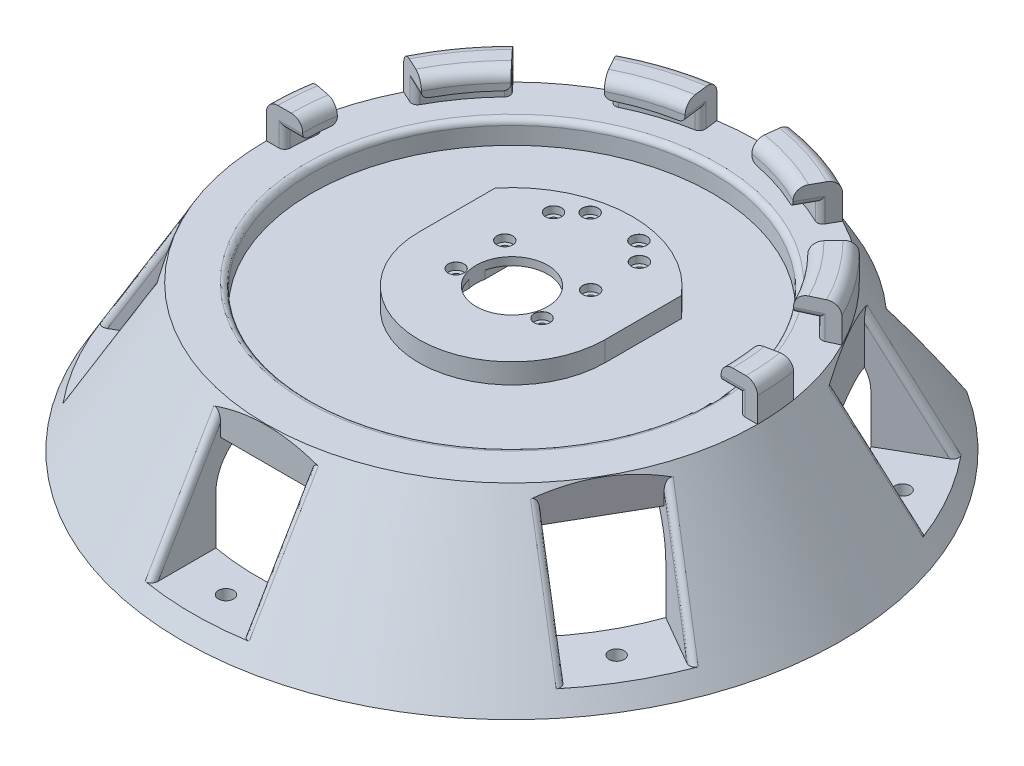
SolidWorks part; units mm, degrees
note: The reader was unsure of these and kept them because the rebuilt part matched: shared geometry of "Sketch3<3>".
material "PLA"
ref_plane "Front Plane" through (0, 0, 0) normal (0, 0, 1) x (1, 0, 0)
ref_plane "Top Plane" through (0, 0, 0) normal (0, 1, 0) x (1, 0, 0)
ref_plane "Right Plane" through (0, 0, 0) normal (1, 0, 0) x (0, 0, -1)
sketch "Sketch1" plane through (0, 0, 0) normal (0, 0, 1) x (1, 0, 0)
  line L0 (0, 0) -> (-85.725, 0)
  line L1 (-85.725, 0) -> (-115.0544, -50.8)
  line L2 (-115.0544, -50.8) -> (0, -50.8)
  line L6 (0, 0) -> (0, -50.8) construction
  line L7 (0, 0) -> (0, -50.8)
  dimension "D1" = 85.725
  dimension "D3" = 50.8
  dimension "D4" = 60
revolve "Revolve1" add sketch "Sketch1" angle 360 about L6
sketch "Sketch2" plane through (0, 0, 0) normal (0, 1, 0) x (1, 0, 0)
  circle A0 centre (0, 0) radius 12.5
  dimension "D1" = 25
extrude "Cut-Extrude1" cut sketch "Sketch2" against normal through all
sketch "Sketch3" plane through (0, 0, 0) normal (0, 1, 0) x (1, 0, 0)
  line L0 (-32.5, 0) -> (-32.5, 26.6036)
  line L1 (-32.5, 26.6036) -> (32.5, 26.6036)
  line L2 (32.5, 26.6036) -> (32.5, 0)
  circle A0 centre (0, 0) radius 32.5
  circle A1 centre (0, 0) radius 70
  circle A2 centre (0, 0) radius 42
  circle M1 centre (0, 0) radius 12.5
  dimension "D1" = 65
  dimension "D2" = 140
  dimension "D3" = 84
extrude "Cut-Extrude2" cut sketch "Sketch3" against normal blind 8 contours A1 A0 L0 L1 L2 | A1 A2
sketch "Sketch7" plane through (0, -50.8, 0) normal (0, -1, 0) x (1, 0, 0)
  line L0 (0, 88.9) -> (0, -161.1) construction
  line L1 (-85.4, 0) -> (85.4, 0) construction
  line L2 (-60, -65.5989) -> (-60, -161.1)
  line L3 (-60, -161.1) -> (60, -161.1)
  line L4 (60, -161.1) -> (60, -65.5989)
  line L5 (-60, -65.5989) -> (60, -65.5989) construction
  arc A2 (60, -65.5989) -> (-60, -65.5989) centre (0, 0) ccw
  dimension "D1" = 177.8
  dimension "D2" = 25.4
  dimension "D3" = 25.4
  dimension "D4" = 120
  dimension "D5" = 250
extrude "Cut-Extrude5" cut sketch "Sketch7" against normal blind 39 contours L3 L4 A2 L2
sketch "Sketch8" plane through (0, 0, 0) normal (0, 1, 0) x (1, 0, 0)
  line L0 (0, 0) -> (0, -115.0544) construction
  line L2 (-15.875, -123.925) -> (15.875, -123.925)
  line L3 (-15.875, -123.925) -> (-15.875, -85.825)
  line L4 (-15.875, -85.825) -> (15.875, -85.825)
  line L5 (15.875, -123.925) -> (15.875, -85.825)
  line L6 (-15.875, -123.925) -> (15.875, -85.825) construction
  line L7 (-15.875, -85.825) -> (15.875, -123.925) construction
  arc A0 (-60, 98.1708) -> (60, 98.1708) centre (0, 0) ccw construction
  point P6 (0, -104.875)
  dimension "D1" = 85.825
  dimension "D2" = 38.1
  dimension "D3" = 31.75
extrude "Cut-Extrude6" cut sketch "Sketch8" against normal blind 44.45
pattern_circular "CirPattern2" count 6 over 360 about axis through (0, 0, 0) along (0, 1, 0) of "Cut-Extrude6"
sketch "Sketch9" plane through (0, 0, 0) normal (0, 1, 0) x (1, 0, 0)
  line L0 (0, 0) -> (0, -115.0544) construction
  arc A0 (-60, 98.1708) -> (60, 98.1708) centre (0, 0) ccw construction
  circle A1 centre (0, -99.8144) radius 2.65
  dimension "D1" = 5.3
  dimension "D2" = 15.24
extrude "Cut-Extrude7" cut sketch "Sketch9" against normal through all
pattern_circular "CirPattern3" count 6 over 360 about axis through (0, 0, 0) along (0, 1, 0) of "Cut-Extrude7"
sketch "Sketch12" plane through (0, 0, 0) normal (0, 0, 1) x (1, 0, 0)
  line L0 (85.725, 0) -> (85.725, 12.7)
  line L1 (85.725, 12.7) -> (73.025, 12.7)
  line L2 (73.025, 12.7) -> (73.025, 6.35)
  line L3 (73.025, 6.35) -> (79.375, 6.35)
  line L4 (79.375, 6.35) -> (79.375, 0)
  line L5 (85.725, 0) -> (-85.725, 0) construction
  line L6 (0, 0) -> (0, 12.7) construction
  line L7 (12.5, 0) -> (-12.5, 0) construction
  line L8 (79.375, 0) -> (85.725, 0)
  point P13 (0, 6.35)
  dimension "D1" = 6.35
  dimension "D2" = 73.025
  dimension "D3" = 79.375
  dimension "D4" = 12.7
  dimension "D5" = 12.7
revolve "Revolve2" add sketch "Sketch12" angle 180 about L6
sketch "Sketch15" plane through (0, -11.8, 0) normal (0, -1, 0) x (1, 0, 0)
  line L0 (0, -1000) -> (0, 49000) construction
  point P1 (-15, 4.5)
  point P4 (-15, -12.5)
  point P5 (-15, -29.5)
  point P6 (-8.5, -35.8)
  point P7 (8.5, -35.8)
  point P8 (15, -29.5)
  point P9 (15, -12.5)
  point P10 (15, 4.5)
  dimension "D1" = 17
  dimension "D2" = 17
  dimension "D3" = 4.5
  dimension "D4" = 15
  dimension "D5" = 8.5
  dimension "D6" = 35.8
sketch "Sketch18" plane through (0, 12.7, 0) normal (0, 1, 0) x (1, 0, 0)
  line L0 (46.6433, 89.7185) -> (70.9138, 72.0849)
  line L1 (0, 201000) -> (0, -249000) construction
  line L2 (-15, 100) -> (-9, 50)
  line L3 (-9, 50) -> (9, 50)
  line L4 (9, 50) -> (15, 100)
  line L5 (-15, 100) -> (15, 100)
  line L6 (36.6704, 35.1608) -> (70.9138, 72.0849)
  line L7 (22.1081, 45.7409) -> (36.6704, 35.1608)
  line L8 (46.6433, 89.7185) -> (22.1081, 45.7409)
  line L9 (90.4704, 45.1675) -> (99.7409, 16.6359)
  line L10 (50.334, 6.8913) -> (99.7409, 16.6359)
  line L11 (44.7717, 24.0104) -> (50.334, 6.8913)
  line L12 (90.4704, 45.1675) -> (44.7717, 24.0104)
  line L13 (99.7409, -16.6359) -> (90.4704, -45.1675)
  line L14 (44.7717, -24.0104) -> (90.4704, -45.1675)
  line L15 (50.334, -6.8913) -> (44.7717, -24.0104)
  line L16 (99.7409, -16.6359) -> (50.334, -6.8913)
  line L17 (70.9138, -72.0849) -> (46.6433, -89.7185)
  line L18 (22.1081, -45.7409) -> (46.6433, -89.7185)
  line L19 (36.6704, -35.1608) -> (22.1081, -45.7409)
  line L20 (70.9138, -72.0849) -> (36.6704, -35.1608)
  line L21 (15, -100) -> (-15, -100)
  line L22 (-9, -50) -> (-15, -100)
  line L23 (9, -50) -> (-9, -50)
  line L24 (15, -100) -> (9, -50)
  line L25 (-46.6433, -89.7185) -> (-70.9138, -72.0849)
  line L26 (-36.6704, -35.1608) -> (-70.9138, -72.0849)
  line L27 (-22.1081, -45.7409) -> (-36.6704, -35.1608)
  line L28 (-46.6433, -89.7185) -> (-22.1081, -45.7409)
  line L29 (-90.4704, -45.1675) -> (-99.7409, -16.6359)
  line L30 (-50.334, -6.8913) -> (-99.7409, -16.6359)
  line L31 (-44.7717, -24.0104) -> (-50.334, -6.8913)
  line L32 (-90.4704, -45.1675) -> (-44.7717, -24.0104)
  line L33 (-99.7409, 16.6359) -> (-90.4704, 45.1675)
  line L34 (-44.7717, 24.0104) -> (-90.4704, 45.1675)
  line L35 (-50.334, 6.8913) -> (-44.7717, 24.0104)
  line L36 (-99.7409, 16.6359) -> (-50.334, 6.8913)
  line L37 (-70.9138, 72.0849) -> (-46.6433, 89.7185)
  line L38 (-22.1081, 45.7409) -> (-46.6433, 89.7185)
  line L39 (-36.6704, 35.1608) -> (-22.1081, 45.7409)
  line L40 (-70.9138, 72.0849) -> (-36.6704, 35.1608)
  point P4 (0, 50)
  point P7 (0, 100)
  point P48 (0, 0)
  dimension "D1" = 18
  dimension "D2" = 50
  dimension "D3" = 30
  dimension "D4" = 50
  dimension "D5" = 10
extrude "Cut-Extrude9" cut sketch "Sketch18" against normal blind 12.7
sketch "Sketch20" plane through (0, -11.8, 0) normal (0, -1, 0) x (1, 0, 0)
  line L0 (-22.5, -33) -> (-12.5, -40)
  line L1 (22.5, 20) -> (-22.5, 20)
  line L2 (22.5, 20) -> (22.5, -40)
  line L3 (22.5, -40) -> (-22.5, -40)
  line L4 (-22.5, 20) -> (-22.5, -40)
  line L5 (22.5, 20) -> (-22.5, -40) construction
  line L6 (22.5, -40) -> (-22.5, 20) construction
  line L7 (-12.5, -40) -> (12.5, -40)
  line L8 (12.5, -40) -> (22.5, -33)
  point P0 (0, -10)
  dimension "D1" = 60
  dimension "D2" = 45
  dimension "D3" = 10
  dimension "D4" = 10
  dimension "D5" = 7
  dimension "D6" = 7
  dimension "D7" = 10
extrude "Cut-Extrude11" cut sketch "Sketch3<3>" against normal blind 1 contours A0 L1 M1 | A0 L1 L0 | L1 A0 | L1 A2 A0 | A0 L2 L1
sketch "Sketch3<3>" plane through (0, 0, 0) normal (0, 1, 0) x (1, 0, 0) same geometry as "Sketch3"
sketch "Sketch22" plane through (0, -1, 0) normal (0, 1, 0) x (1, 0, 0)
  circle A0 centre (-15, 12.5) radius 1.4
  circle A1 centre (-15, 29.5) radius 1.4
  circle A2 centre (-8.5, 35.8) radius 1.4
  circle A3 centre (8.5, 35.8) radius 1.4
  circle A4 centre (15, 29.5) radius 1.4
  circle A5 centre (15, 12.5) radius 1.4
  circle A6 centre (15, -4.5) radius 1.4
  circle A7 centre (-15, -4.5) radius 1.4
  dimension "D1" = 17
  dimension "D2" = 17
  dimension "D3" = 2.8
  dimension "D4" = 2.8
  dimension "D5" = 2.8
  dimension "D6" = 2.8
  dimension "D7" = 2.8
  dimension "D8" = 2.8
  dimension "D9" = 2.8
  dimension "D10" = 2.8
  dimension "D11" = 17
  dimension "D12" = 30
  dimension "D13" = 30
  dimension "D14" = 30
  dimension "D15" = 17
  dimension "D16" = 17
  dimension "D17" = 6.3
  dimension "D18" = 6.3
  dimension "D19" = 35.8
  dimension "D20" = 8.5
  dimension "D21" = 35.8
  dimension "D22" = 15
  dimension "D23" = 19.5256
  dimension "D24" = 15.6605
hole_wizard "CBORE for M2.5 SHCS1" positions "Sketch23" profile "Sketch24" counterbore size "M2.5" standard "ANSI Metric" end condition through all
sketch "Sketch23" plane through (0, -1, 0) normal (0, 1, 0) x (1, 0, 0)
  point P0 (-15, -4.5)
  point P3 (-15, 12.5)
  point P6 (-15, 29.5)
  point P9 (-8.5, 35.8)
  point P12 (8.5, 35.8)
  point P15 (15, 29.5)
  point P18 (15, 12.5)
  point P21 (15, -4.5)
sketch "Sketch24" plane through (-15, -1, 4.5) normal (1, 0, 0) x (0, 0, 1)
  line L0 (0, 0) -> (0, 49.8)
  line L1 (0, 49.8) -> (1.45, 49.8)
  line L3 (1.45, 49.8) -> (1.45, 2.5)
  line L4 (2.75, 2.5) -> (1.45, 2.5)
  line L5 (2.75, 2.5) -> (2.75, 0.025)
  line L6 (2.75, 0.025) -> (2.775, 0)
  line L7 (2.775, 0) -> (0, 0)
  line L8 (-2.75, 0.025) -> (-2.775, 0) construction
  line L11 (0, -6.35) -> (0, 107.95) construction
  dimension "Thru Hole Dia." = 2.9
  dimension "Thru Hole Depth" = 49.8
  dimension "C'Bore Dia." = 5.5
  dimension "C'Bore Depth" = 2.5
  dimension "Near C'Sink Dia." = 5.55
  dimension "Near C'Sink Angle" = 90
fillet "Fillet1" radius 4 12 edges at (85.4509, 12.7, -6.8497) (69.353, 12.7, -50.3879) (26.4905, 12.7, -81.5293) (-26.4905, 12.7, -81.5293) (-69.353, 12.7, -50.3879) (-85.4509, 12.7, -6.8497) (-72.8088, 12.7, -5.6148) (-59.0785, 12.7, -42.923) (-22.566, 12.7, -69.4509) (22.566, 12.7, -69.4509) (59.0785, 12.7, -42.923) (72.8088, 12.7, -5.6148)
fillet "Fillet2" radius 2 12 edges at (75.2789, 6.35, -11.8112) (76.2, 6.35, 0) (53.9595, 6.35, -53.8033) (67.8444, 6.35, -34.6924) (12.0293, 6.35, -75.2444) (34.4956, 6.35, -67.9447) (-12.0293, 6.35, -75.2444) (-34.4956, 6.35, -67.9447) (-53.9595, 6.35, -53.8033) (-67.8444, 6.35, -34.6924) (-75.2789, 6.35, -11.8112) (-76.2, 6.35, 0)
fillet "Fillet3" radius 2 12 edges at (-78.3963, 4.175, -12.4261) (-56.1201, 4.175, -56.1331) (-70.7278, 4.175, -36.0273) (-12.4079, 4.175, -78.3992) (56.1201, 4.175, -56.1331) (78.3963, 4.175, -12.4261) (-79.375, 4.175, 0) (-36.0437, 4.175, -70.7195) (12.4079, 4.175, -78.3992) (36.0437, 4.175, -70.7195) (70.7278, 4.175, -36.0273) (79.375, 4.175, 0)
fillet "Fillet4" radius 2 10 edges
fillet "Fillet5" radius 2 1 edges at (0, 0, 70)
fillet "Fillet6" radius 16 4 edges at (88.9, -11.8, 0) (-88.9, -11.8, 0) (-44.45, -11.8, 76.9897) (44.45, -11.8, 76.9897)
fillet "Fillet7" radius 16 1 edges at (64.036, -11.8, -61.6652)
fillet "Fillet8" radius 16 1 edges at (-64.036, -11.8, -61.6652)
fillet "Fillet9" radius 1 2 edges
sketch "Sketch28" plane through (0, -11.8, 0) normal (0, -1, 0) x (1, 0, 0)
  line L0 (9.2, 12) -> (-9.2, 12)
  line L1 (-12.2, 9) -> (-12.2, -30)
  line L2 (-9.2, -33) -> (9.2, -33)
  line L3 (12.2, -30) -> (12.2, 9)
  arc A0 (-9.2, 12) -> (-12.2, 9) centre (-9.2, 9) ccw
  arc A1 (-12.2, -30) -> (-9.2, -33) centre (-9.2, -30) ccw
  arc A2 (9.2, -33) -> (12.2, -30) centre (9.2, -30) ccw
  arc A3 (12.2, 9) -> (9.2, 12) centre (9.2, 9) ccw
extrude "Cut-Extrude12" cut sketch "Sketch28" against normal offset from surface (8.05 mm away) 2.75
extrude "Cut-Extrude15" cut sketch "Sketch20" against normal offset from surface (5.3 mm away) 2.75
